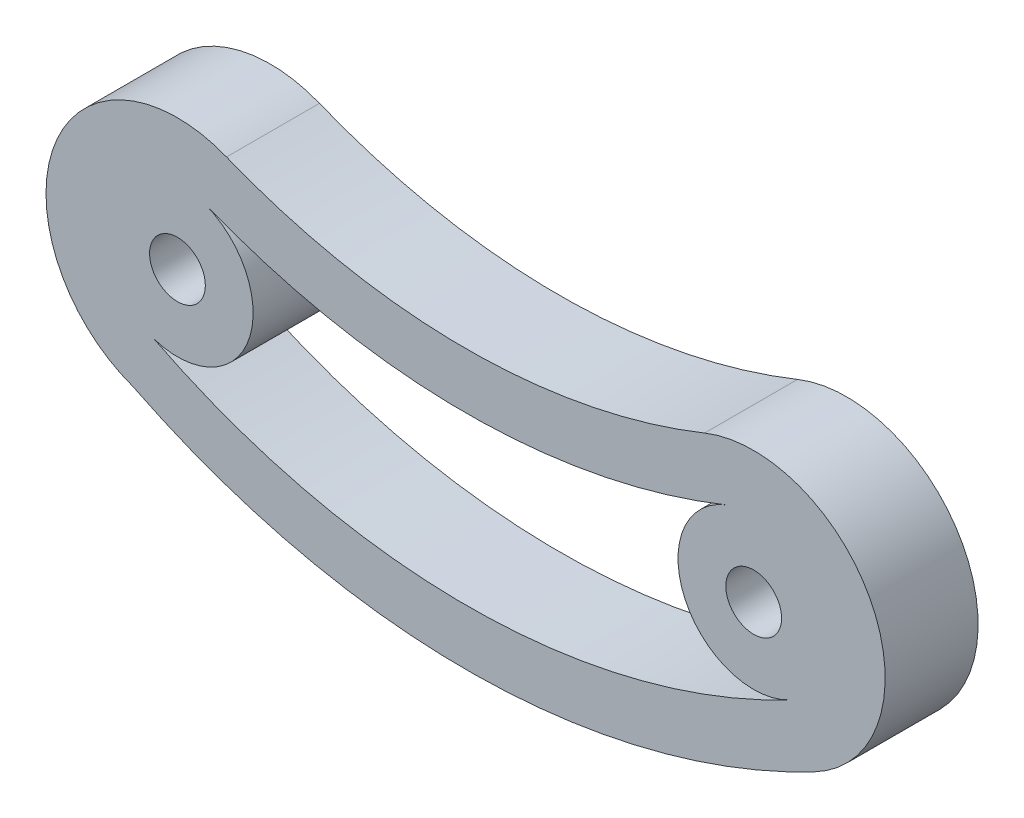
SolidWorks part; units mm, degrees
material "1060 Alloy"
ref_plane "Front Plane" through (0, 0, 0) normal (0, 0, 1) x (1, 0, 0)
ref_plane "Top Plane" through (0, 0, 0) normal (0, 1, 0) x (1, 0, 0)
ref_plane "Right Plane" through (0, 0, 0) normal (1, 0, 0) x (0, 0, -1)
sketch "Sketch1" plane through (0, 0, 0) normal (0, 0, 1) x (1, 0, 0)
  line L0 (0, 0) -> (31, 0)
  line L1 (0, -5) -> (31, -5)
  line L2 (0, 5) -> (31, 5)
  circle A0 centre (31, 0) radius 1.5
  circle A1 centre (0, 0) radius 1.5
  arc A2 (0, -5) -> (0, 5) centre (0, 0) cw
  arc A3 (31, -5) -> (31, 5) centre (31, 0) ccw
  dimension "D1" = 3
extrude "Extrude1" add sketch "Sketch1" along normal blind 5 contours L1 A3 L2 A2 A1 A0 region at (-4.578, 0, 0)
sketch "Sketch2" plane through (0, 0, 5) normal (0, 0, 1) x (1, 0, 0)
  line L1 (15.5, 5) -> (15.5, -10)
  line L2 (0, 5) -> (31, 5) construction
  arc A0 (36, 0) -> (-5, 0) centre (15.5, 16.0125) cw
  arc A1 (36, 0) -> (31, 5) centre (33.5, 2.5) ccw
  arc A2 (31, -5) -> (31, 5) centre (31, 0) ccw construction
  arc A3 (0, 5) -> (0, -5) centre (0, 0) ccw construction
  arc A4 (31, 5) -> (0, 5) centre (15.5, 21.0125) cw
  arc A5 (-5, 0) -> (0, 5) centre (-2.5, 2.5) cw
  line M3 (0, -5) -> (31, -5)
  arc M4 (31, -5) -> (31, 5) centre (31, 0) ccw
  line M5 (31, 5) -> (0, 5)
  arc M6 (0, 5) -> (0, -5) centre (0, 0) ccw
  dimension "D2" = 5
  dimension "D1" = 15
extrude "Boss-Extrude2" add sketch "Sketch2" against normal blind 5 contours A1 M4 | A0 L1 M3 | A0 L1 M3 | A5 M6 region at (21.3318, -7.0174, 5) region at (9.6682, -7.0174, 5) region at (34.927, 3.927, 5) region at (-3.927, 3.927, 5)
extrude "Cut-Extrude4" cut sketch "Sketch2<6>" against normal blind 5 contours A0 M4 M3 | A0 M3 M6 | A4 L1 M5 | A4 L1 M5 region at (21.4396, 2.4578, 5) region at (9.5604, 2.4578, 5) region at (33.916, -3.0126, 5) region at (-2.916, -3.0126, 5)
sketch "Sketch2<6>" plane through (0, 0, 5) normal (0, 0, 1) x (1, 0, 0) same geometry as "Sketch2"
sketch "Sketch4" plane through (0, 0, 0) normal (0, 0, -1) x (-1, 0, 0)
  arc A5 (-3.5109, -1.2502) -> (-2.3631, -2.8819) centre (0, 0) ccw
  arc A6 (-28.5529, -2.94) -> (-27.4015, -1.2971) centre (-31, 0) ccw
  arc A8 (-33.1122, 2.8693) -> (2.1122, 2.8693) centre (-15.5, 21.0125) ccw
  arc A9 (-33.1122, 2.8693) -> (-33.7951, 2.0531) centre (-33.5, 2.5) ccw
  arc A10 (-33.7951, 2.0531) -> (2.7951, 2.0531) centre (-15.5, 16.0125) ccw
  arc A11 (2.7951, 2.0531) -> (2.1122, 2.8693) centre (2.5, 2.5) ccw
  arc A12 (-27.4015, -1.2971) -> (-3.5109, -1.2502) centre (-15.5, 21.0125) ccw
  arc A14 (-28.5529, -2.94) -> (-2.3631, -2.8819) centre (-15.5, 16.0125) ccw
  dimension "D1" = 3
extrude "Cut-Extrude5" cut sketch "Sketch4" against normal blind 5
sketch "Sketch5" plane through (0, 0, 0) normal (0, 0, -1) x (-1, 0, 0)
  circle A0 centre (0, 0) radius 7.0711
  circle A1 centre (-31, 0) radius 7.0711
  arc M7 (0, 5) -> (-31, 5) centre (-15.5, 21.0125) cw
  arc M8 (-31, 5) -> (-36, 0) centre (-33.5, 2.5) ccw
  arc M9 (-36, 0) -> (5, 0) centre (-15.5, 16.0125) ccw
  arc M10 (5, 0) -> (0, 5) centre (2.5, 2.5) ccw
extrude "Boss-Extrude3" add sketch "Sketch5" against normal blind 5 contours A1 M7 M8 | A1 M8 M9 | A0 M10 M7 | A0 M9 M10 region at (-3.5179, -3.3541, 0) region at (2.7948, 4.3745, 0) region at (34.5179, -3.3541, 0) region at (28.2052, 4.3745, 0)
sketch "Sketch6" plane through (0, 0, 0) normal (0, 0, -1) x (-1, 0, 0)
  arc A0 (-2.6395, 6.5599) -> (-28.3605, 6.5599) centre (-15.5, 38.5218) cw
  arc A1 (-2.5997, -6.5758) -> (-7.0605, 0.3867) centre (0, 0) ccw construction
  arc A2 (-23.9395, 0.3867) -> (-28.4003, -6.5758) centre (-31, 0) ccw construction
  arc A3 (2.3961, -6.6527) -> (-34.2887, -6.2598) centre (-15.5624, 29.3845) cw
  arc M1 (-23.9395, 0.3867) -> (-28.4003, -6.5758) centre (-31, 0) ccw
  arc M2 (-28.4003, -6.5758) -> (-2.5997, -6.5758) centre (-15.5, 16.0125) ccw
  arc M3 (-2.5997, -6.5758) -> (-7.0605, 0.3867) centre (0, 0) ccw
  arc M4 (-7.0605, 0.3867) -> (-23.9395, 0.3867) centre (-15.5, 21.0125) cw
  arc M5 (-28.5529, -2.94) -> (-27.4015, -1.2971) centre (-31, 0) ccw
  arc M6 (-27.4015, -1.2971) -> (-3.5109, -1.2502) centre (-15.5, 21.0125) ccw
  arc M7 (-3.5109, -1.2502) -> (-2.3631, -2.8819) centre (0, 0) ccw
  arc M8 (-2.3631, -2.8819) -> (-28.5529, -2.94) centre (-15.5, 16.0125) cw
extrude "Boss-Extrude4" add sketch "Sketch6" against normal blind 5 contours A0 M3 M1 M4 | A3 M3 M2 M1 | M5 M8 M7 M6 region at (15.5, 2.0626, 0) region at (15.9897, -10.5074, 0) region at (15.4619, -4.5726, 0)
sketch "Sketch7" plane through (0, 0, 0) normal (0, 0, -1) x (-1, 0, 0)
  circle A4 centre (-31, 0) radius 4.0711
  circle A5 centre (0, 0) radius 4.0711
  arc A8 (-32.8934, -3.604) -> (1.2332, -3.8798) centre (-15.5624, 29.3845) ccw
  arc A9 (1.2332, -3.8798) -> (-1.5197, 3.7768) centre (0, 0) ccw
  arc A10 (-29.4803, 3.7768) -> (-1.5197, 3.7768) centre (-15.5, 38.5218) ccw
  arc A11 (-29.4803, 3.7768) -> (-32.8934, -3.604) centre (-31, 0) ccw
  arc A12 (-32.8934, -3.604) -> (1.2332, -3.8798) centre (-15.5624, 29.3845) ccw
  arc A13 (1.2332, -3.8798) -> (-1.5197, 3.7768) centre (0, 0) ccw
  arc A14 (-29.4803, 3.7768) -> (-1.5197, 3.7768) centre (-15.5, 38.5218) ccw
  arc A15 (-29.4803, 3.7768) -> (-32.8934, -3.604) centre (-31, 0) ccw
  dimension "D1" = 3
extrude "Cut-Extrude6" cut sketch "Sketch7" against normal blind 5 contours A14 A4 A12 A5 region at (15.5258, -2.8514, 0)
move or copy body "Body-Move/Copy1" [suppressed] bodies to move or copy 112
move or copy body "Body-Move/Copy2" [suppressed] bodies to move or copy 112
